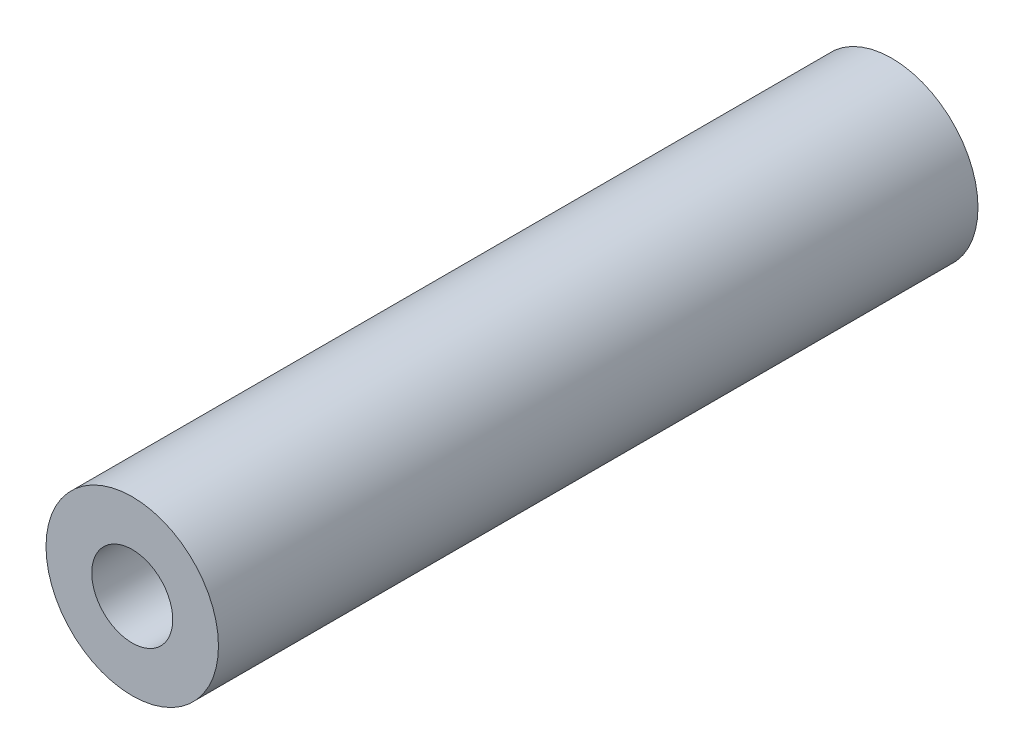
SolidWorks part; units mm, degrees
ref_plane "Front Plane" through (0, 0, 0) normal (0, 0, 1) x (1, 0, 0)
ref_plane "Top Plane" through (0, 0, 0) normal (0, 1, 0) x (1, 0, 0)
ref_plane "Right Plane" through (0, 0, 0) normal (1, 0, 0) x (0, 0, -1)
sketch "Sketch1" plane through (0, 0, 0) normal (0, 0, 1) x (1, 0, 0)
  circle A0 centre (0, 0) radius 9.525
  circle A1 centre (0, 0) radius 4.4751
  circle A3 centre (0, 0) radius 3.9751 construction
  circle A4 centre (0, 0) radius 3.9751 construction
  dimension "D1" = 19.05
  dimension "D2" = 0.5
extrude "Boss-Extrude1" add sketch "Sketch1" against normal up to surface (83.8962 mm away)
